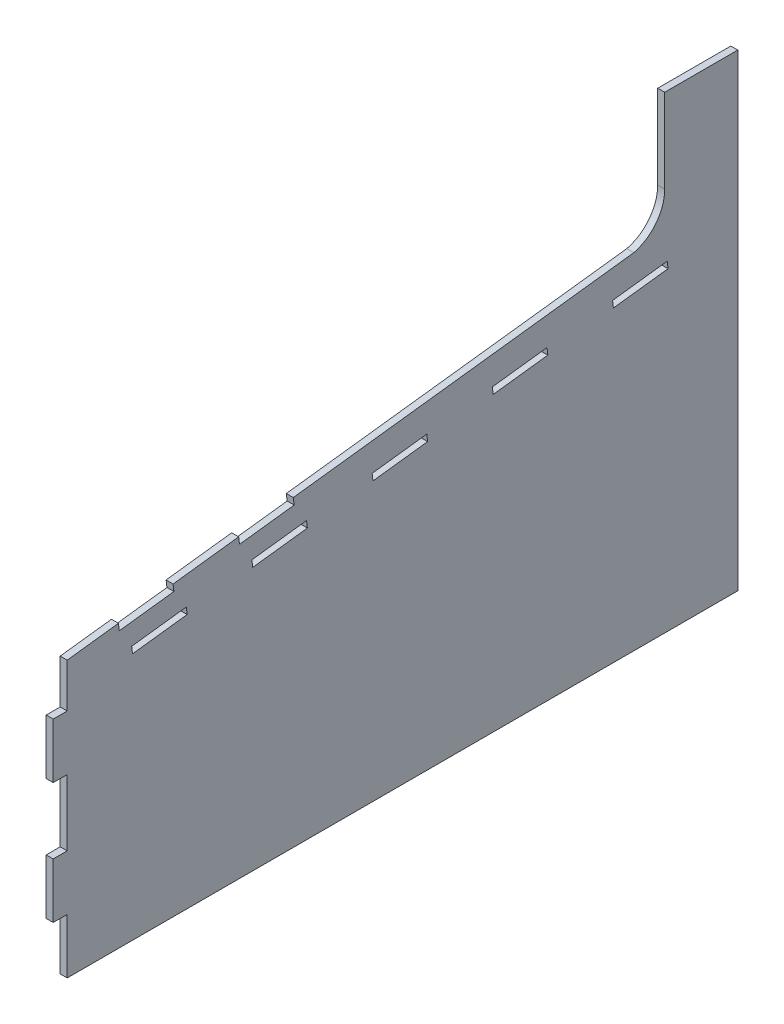
SolidWorks part; units mm, degrees
material "Beech"
ref_plane "Front Plane" through (0, 0, 0) normal (0, 0, 1) x (1, 0, 0)
ref_plane "Top Plane" through (0, 0, 0) normal (0, 1, 0) x (1, 0, 0)
ref_plane "Right Plane" through (0, 0, 0) normal (1, 0, 0) x (0, 0, -1)
sketch "Sketch1" plane through (0, 0, 0) normal (1, 0, 0) x (0, 0, -1)
  line L1 (0, 0) -> (609, 0)
  line L2 (0, 0) -> (0, 50)
  line L4 (609, 0) -> (609, 250)
  line L6 (609, 250) -> (609, 425.32)
  line L7 (609, 425.32) -> (542.65, 425.32)
  line L8 (542.65, 349.09) -> (542.65, 425.32)
  line L9 (0, 250) -> (609, 250) construction
  line L10 (514.5695, 313.1812) -> (609, 324.7758) construction
  line L11 (-12.7, 160) -> (-12.7, 210)
  line L12 (0, 50) -> (-12.7, 50)
  line L14 (0, 100) -> (-12.7, 100)
  line L15 (-12.7, 50) -> (-12.7, 100)
  line L16 (0, 160) -> (-12.7, 160)
  line L18 (0, 210) -> (-12.7, 210)
  line L19 (0, 210) -> (0, 250)
  line L21 (0, 100) -> (0, 160)
  line L33 (0, 250) -> (514.5695, 313.1812) construction
  line L34 (0, 250) -> (514.5695, 313.1812)
  arc A0 (514.5695, 313.1812) -> (542.65, 349.09) centre (505.65, 349.09) ccw
  dimension "D4" = 37
  dimension "D1" = 609
  dimension "D2" = 250
  dimension "D3" = 66.35
  dimension "D5" = 7
  dimension "D6" = 175.32
  dimension "D7" = 76.23
  dimension "D8" = 12.7
  dimension "D9" = 50
  dimension "D10" = 50
  dimension "D11" = 2
  dimension "D12" = 40
extrude "Boss-Extrude1" add sketch "Sketch1" along normal blind 6.35
sketch "Sketch2" plane through (6.35, 0, 0) normal (1, 0, 0) x (0, 0, -1)
  line L0 (514.5695, 313.1812) -> (609, 324.7758) construction
  line L1 (609, 0) -> (609, 425.32) construction
  line L2 (205.3392, 275.2125) -> (155.7119, 269.119)
  line L3 (0, 224.4093) -> (609, 299.185) construction
  line L4 (0, 50) -> (0, 0) construction
  line L5 (58.5602, 231.5995) -> (59.3341, 225.2969)
  line L6 (59.3341, 225.2969) -> (108.9614, 231.3903)
  line L7 (108.9614, 231.3903) -> (108.1875, 237.693)
  line L8 (108.1875, 237.693) -> (58.5602, 231.5995)
  line L9 (217.3676, 251.0986) -> (167.7403, 245.0052)
  line L10 (167.7403, 245.0052) -> (168.5142, 238.7025)
  line L11 (168.5142, 238.7025) -> (218.1415, 244.796)
  line L12 (218.1415, 244.796) -> (217.3676, 251.0986)
  line L13 (326.5477, 264.5043) -> (276.9204, 258.4108)
  line L14 (276.9204, 258.4108) -> (277.6942, 252.1081)
  line L15 (277.6942, 252.1081) -> (327.3216, 258.2016)
  line L16 (327.3216, 258.2016) -> (326.5477, 264.5043)
  line L17 (435.7278, 277.9099) -> (386.1005, 271.8164)
  line L18 (386.1005, 271.8164) -> (386.8743, 265.5138)
  line L19 (386.8743, 265.5138) -> (436.5016, 271.6072)
  line L20 (436.5016, 271.6072) -> (435.7278, 277.9099)
  line L21 (544.9078, 291.3155) -> (495.2805, 285.2221)
  line L22 (495.2805, 285.2221) -> (496.0544, 278.9194)
  line L23 (496.0544, 278.9194) -> (545.6817, 285.0129)
  line L24 (545.6817, 285.0129) -> (544.9078, 291.3155)
  line L25 (155.7119, 269.119) -> (156.4858, 262.8163)
  line L26 (514.5695, 313.1812) -> (0, 250) construction
  line L27 (0, 224.4093) -> (-3.0955, 249.6199) construction
  line L28 (-3.0955, 249.6199) -> (0, 250) construction
  line L29 (46.5318, 255.7134) -> (47.3057, 249.4107)
  line L30 (47.3057, 249.4107) -> (96.933, 255.5042)
  line L31 (96.933, 255.5042) -> (96.1591, 261.8069)
  line L32 (96.1591, 261.8069) -> (46.5318, 255.7134)
  line L33 (156.4858, 262.8163) -> (206.1131, 268.9098)
  line L34 (206.1131, 268.9098) -> (205.3392, 275.2125)
  dimension "D1" = 25.4
  dimension "D2" = 50
  dimension "D3" = 6.35
  dimension "D4" = 59
  dimension "D5" = 90
  dimension "D6" = 6.35
  dimension "D7" = 50
  dimension "D8" = 50
  dimension "D9" = 2
extrude "Cut-Extrude1" cut sketch "Sketch2" against normal blind 6.35
